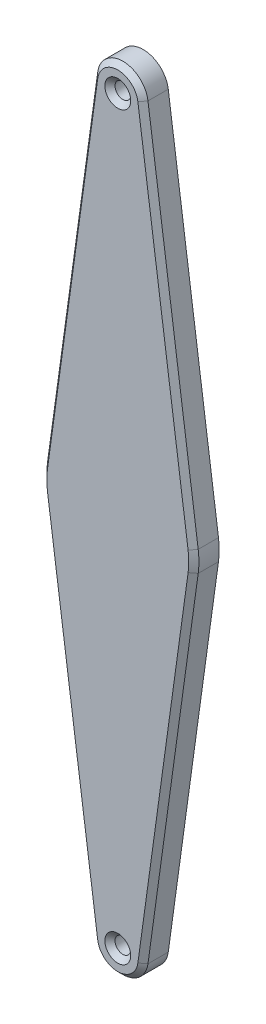
SolidWorks part; units mm, degrees
ref_plane "Front Plane" through (0, 0, 0) normal (0, 0, 1) x (1, 0, 0)
ref_plane "Top Plane" through (0, 0, 0) normal (0, 1, 0) x (1, 0, 0)
ref_plane "Right Plane" through (0, 0, 0) normal (1, 0, 0) x (0, 0, -1)
sketch "Sketch1" plane through (0, 0, 0) normal (0, 0, 1) x (1, 0, 0)
  line L1 (191, 68) -> (85, 68)
  line L2 (85, 68) -> (85, 141) construction
  line L3 (89.9529, 141.6849) -> (99.8586, 70.0548)
  line L8 (0, 136) -> (0, 0)
  line L9 (0, 0) -> (191, 0)
  line L10 (191, 0) -> (191, 136)
  line L11 (191, 136) -> (0, 136)
  line L12 (80.0471, 141.6849) -> (70.1414, 70.0548)
  line L13 (89.9529, -5.6849) -> (99.8586, 65.9452)
  line L14 (80.0471, -5.6849) -> (70.1414, 65.9452)
  circle A0 centre (85, 68) radius 15
  circle A1 centre (85, 141) radius 5
  circle A2 centre (85, -5) radius 5
  dimension "D2" = 30
  dimension "D4" = 10
  dimension "D3" = 5
extrude "Boss-Extrude1" add sketch "Sketch1" along normal blind 5 contours L2 A0 L3 L11 | A0 L2 L11 L12 | A1 | A1 L11 L3 | A1 L12 L11 | L1 L2 A0 | L2 L1 A0 | A0 L14 L9 L13 | L14 A2 L9 | L9 A2 L13 | A2 region at (82.8779, 65.8779, 0) region at (91.3662, 74.3662, 0) region at (90.3088, 104.3689, 0) region at (85, 31.6311, 0) region at (89.2502, -1.2971, 0) region at (89.2502, 137.2971, 0) region at (79.6912, 104.3689, 0) region at (80.7498, -1.2971, 0) region at (85, -5, 0) region at (89.8471, 141.3336, 0) region at (80.7498, 137.2971, 0)
chamfer "Chamfer1" distance 1 angle 45 8 edges at (75.0943, 30.1301, 5) (70, 68, 5) (75.0943, 105.8699, 5) (85, 146, 5) (94.9057, 105.8699, 5) (100, 68, 5) (94.9057, 30.1301, 5) (85, -10, 5)
sketch "Sketch6" plane through (0, 0, 5) normal (0, 0, 1) x (1, 0, 0)
  circle A0 centre (85, 141) radius 1.55
  dimension "D1" = 3.1
extrude "Cut-Extrude2" cut sketch "Sketch6" against normal up to next contours A0 region at (85, 141, 5)
chamfer "Chamfer3" distance 1 angle 45 1 edges at (86.55, 141, 5)
sketch "Sketch7" plane through (0, 0, 5) normal (0, 0, 1) x (1, 0, 0)
  line L1 (190.7957, 61.4224) -> (85, 68) construction
  line L2 (190.7957, 61.4224) -> (85, 68) construction
ref_axis "Axis2" through (85, 68, 5) along (0, 0, -1)
sketch "Sketch8" plane through (0, 0, 0) normal (0, 0, -1) x (-1, 0, 0)
  line L0 (-100, 68) -> (-70, 68) construction
  arc A0 (-99.8586, 70.0548) -> (-99.8586, 65.9452) centre (-85, 68) ccw construction
  arc A1 (-70.1414, 65.9452) -> (-70.1414, 70.0548) centre (-85, 68) ccw construction
ref_axis "Axis3" through (100, 68, 0) along (-1, 0, 0)
ref_plane "Plane3" through (0, 68, 0) normal (0, -1, 0) x (-1, 0, 0)
mirror "Mirror2" about plane through (0, 68, 0) normal (0, -1, 0) of "Cut-Extrude2", "Chamfer3"
